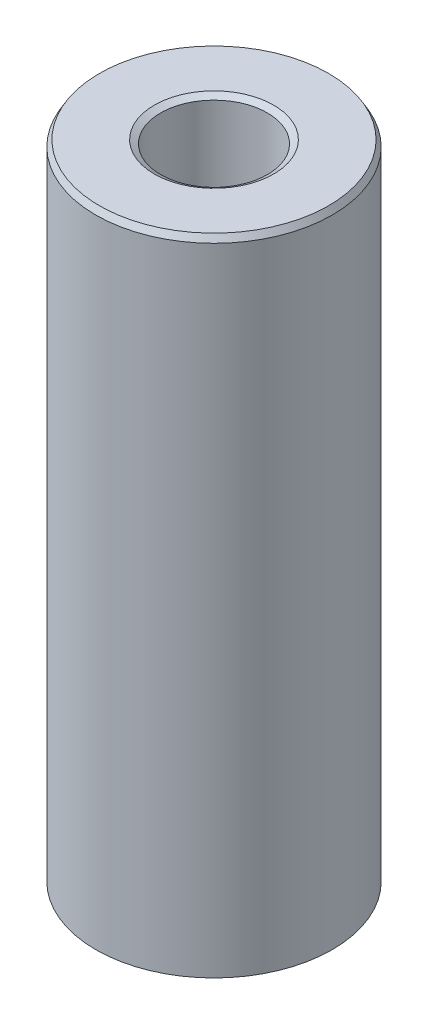
SolidWorks part; units mm, degrees
ref_plane "Front Plane" through (0, 0, 0) normal (0, 0, 1) x (1, 0, 0)
ref_plane "Top Plane" through (0, 0, 0) normal (0, 1, 0) x (1, 0, 0)
ref_plane "Right Plane" through (0, 0, 0) normal (1, 0, 0) x (0, 0, -1)
sketch "Sketch1" plane through (0, 0, 0) normal (0, 1, 0) x (1, 0, 0)
  circle A0 centre (0, 0) radius 60
  dimension "SLEEVE_OD" = 120
extrude "Boss-Extrude1" add sketch "Sketch1" along normal blind 327.8928
sketch "Sketch2" plane through (0, 0, 0) normal (0, 1, 0) x (1, 0, 0)
  circle A0 centre (0, 0) radius 27.1191
  dimension "BORE_D" = 54.2382
extrude "Cut-Extrude1" cut sketch "Sketch2" along normal through all
chamfer "Chamfer1" distance 3.1766 angle 30 4 edges at (0, 327.8928, 27.1191) (0, 0, 27.1191) (0, 0, 60) (0, 327.8928, 60) first distance on face at (0, 327.8928, 27.1191) first distance on face at (0, 0, 27.1191) first distance on face at (0, 327.8928, 60)
